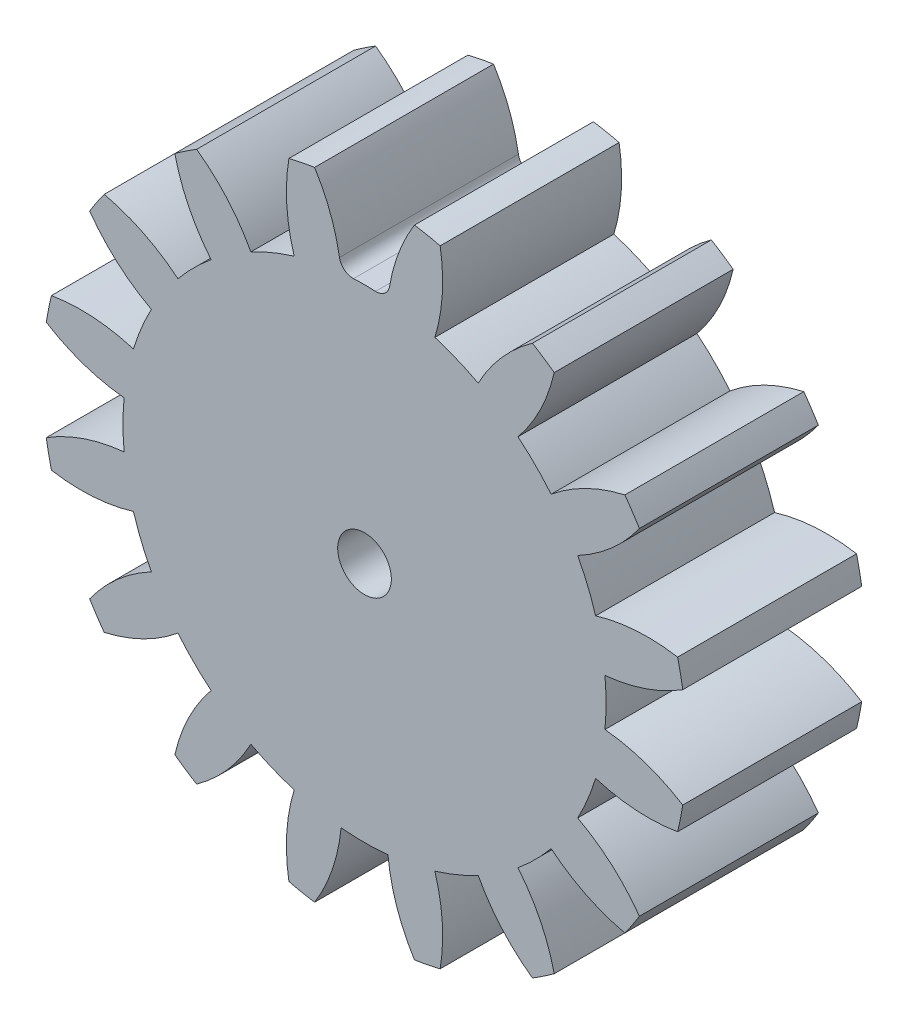
SolidWorks part; units mm, degrees
ref_plane "Front Plane" through (0, 0, 0) normal (0, 0, 1) x (1, 0, 0)
ref_plane "Top Plane" through (0, 0, 0) normal (0, 1, 0) x (1, 0, 0)
ref_plane "Right Plane" through (0, 0, 0) normal (1, 0, 0) x (0, 0, -1)
sketch "Sketch1" plane through (0, 0, 0) normal (0, 0, 1) x (1, 0, 0)
  circle A0 centre (0, 0) radius 18
  circle A1 centre (0, 0) radius 1.5
  dimension "D1" = 3
  dimension "D2" = 36
extrude "Boss-Extrude1" add sketch "Sketch1" along normal mid plane 10
sketch "Sketch2" plane through (0, 0, 0) normal (0, 0, 1) x (1, 0, 0)
  line L0 (0, 0) -> (0, 18) construction
  line L1 (0, 0) -> (-1.3096, 13.4363) construction
  line L2 (0, 10.7625) -> (-3.5688, 20.5678) construction
  arc A0 (1.8665, 15.8908) -> (-1.8665, 15.8908) centre (0, 0) ccw construction
  arc A1 (1.3096, 13.4363) -> (-1.3096, 13.4363) centre (0, 0) ccw
  circle A2 centre (0, 0) radius 18 construction
  arc A3 (2.7904, 17.7824) -> (-2.7904, 17.7824) centre (0, 0) ccw
  arc A4 (-1.3096, 13.4363) -> (-2.7904, 17.7824) centre (-11.2801, 12.4645) ccw
  arc A5 (1.3096, 13.4363) -> (2.7904, 17.7824) centre (11.2801, 12.4645) cw
  dimension "D1" = 32
  dimension "D2" = 4.5
  dimension "D3" = 20
  dimension "D4" = 3.7416
extrude "Cut-Extrude1" cut sketch "Sketch2" against normal through all both and the other way through all
fillet "Fillet1" radius 0.76 2 edges at (1.3096, 13.4363, 0) (-1.3096, 13.4363, 0)
pattern_circular "CirPattern3" count 16 over 360 about axis through (0, 0, 5) along (0, 0, -1) of "Cut-Extrude1"
equation "\"Module\"= 02"
equation "\"Pressure Angle\"= 20"
equation "\"Bore\"= 3"
equation "\"NumTeeth\"= 16"
equation "\"D1@Sketch1\"=\"Bore\""
equation "\"D2@Sketch1\"=(\"NumTeeth\"+2)*\"Module\""
equation "\"D1@Sketch2\"=\"NumTeeth\"*\"Module\""
equation "\"ToothDepth\"= IIF ( \"Module\" < 1.25 , 2.4 * \"Module\" , 2.25 * \"Module\" )"
equation "\"D2@Sketch2\"=\"ToothDepth\""
equation "\"D3@Sketch2\"=\"Pressure Angle\""
equation "\"D4@Sketch2\"=((\"Module\"*PI)/2)+0.3*\"Module\""
equation "\"D1@Fillet1\"=\"Module\"*0.38"
equation "\"D1@CirPattern3\"=\"NumTeeth\""
